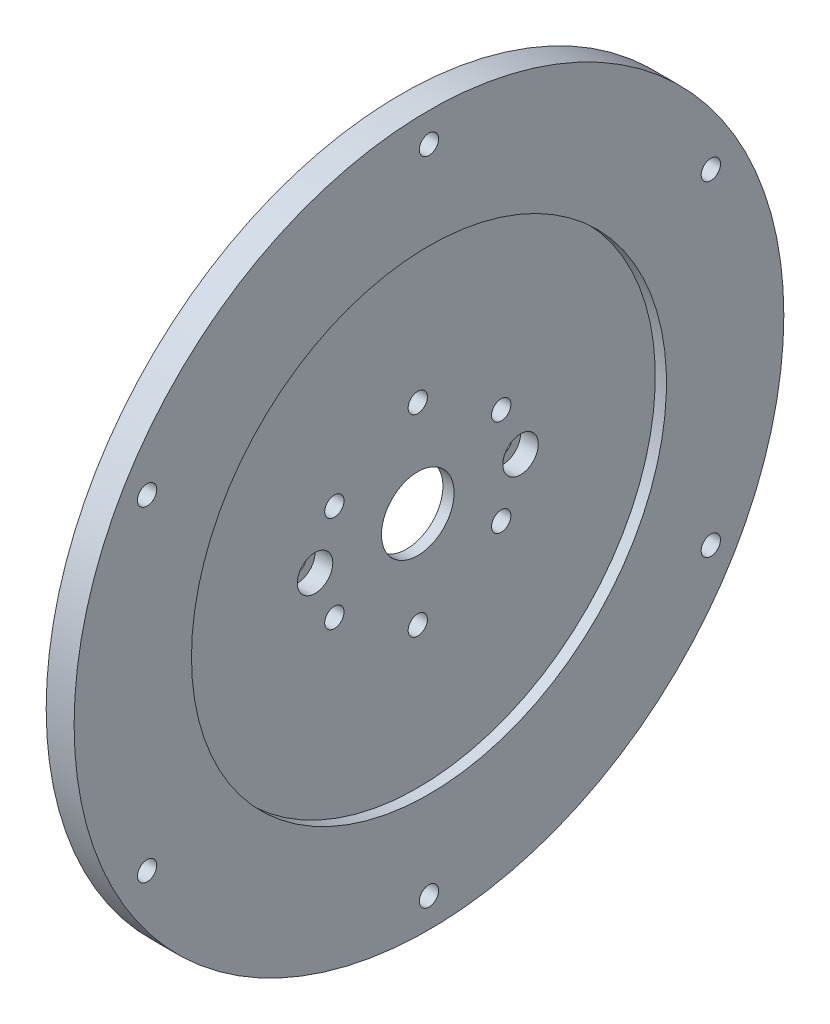
SolidWorks part; units mm, degrees
ref_plane "Front Plane" through (0, 0, 0) normal (0, 0, 1) x (1, 0, 0)
ref_plane "Top Plane" through (0, 0, 0) normal (0, 1, 0) x (1, 0, 0)
ref_plane "Right Plane" through (0, 0, 0) normal (1, 0, 0) x (0, 0, -1)
sketch "Sketch1" plane through (0, 0, 0) normal (0, 0, 1) x (1, 0, 0)
  line L0 (0, 0) -> (58.591, 0) construction
  line L2 (0, 0) -> (19, 0)
  line L3 (0, 0) -> (0, 2.5)
  line L4 (0, 2.5) -> (19, 2.5)
  line L5 (19, 0) -> (19, 2.5)
  line L6 (6, 2.5) -> (6, 6)
  line L11 (6, 6) -> (10, 6)
  line L16 (13, 6) -> (13, 3)
  line L17 (13, 3) -> (13.6604, 3)
  line L18 (13.6604, 3) -> (13.6604, 2.5)
  line L19 (13.6604, 2.5) -> (6, 2.5)
  line L22 (13.6604, 2.5) -> (16.1604, 2.5)
  line L23 (13.6604, 2.5) -> (13.6604, 4)
  line L24 (13.6604, 4) -> (16.1604, 4)
  line L25 (16.1604, 2.5) -> (16.1604, 4)
  line L27 (6, 6) -> (10, 6)
  line L28 (6, 6) -> (6, 9)
  line L29 (6, 9) -> (10, 9)
  line L30 (10, 6) -> (10, 9)
  line L31 (6, 9) -> (6, 8.25)
  line L32 (6, 8.25) -> (5, 8.25)
  line L33 (8.58, 22.001) -> (8.58, 12.476) construction
  line L34 (5, 12.476) -> (12.16, 12.476)
  line L35 (10, 9) -> (12.16, 9)
  line L36 (5, 7.5) -> (3, 7.5)
  line L37 (5, 8.25) -> (5, 12.476)
  line L38 (5, 7.5) -> (5, 14)
  line L39 (5, 14) -> (3, 14)
  line L40 (3, 7.5) -> (3, 14)
  line L41 (5, 22.001) -> (12.16, 22.001)
  line L42 (5, 22.001) -> (5, 30.1625)
  line L43 (5, 30.1625) -> (12.16, 30.1625)
  line L44 (12.16, 22.001) -> (12.16, 30.1625)
  line L49 (16.6604, 22.001) -> (16.6604, 7.5)
  line L51 (23.0604, 7.5) -> (23.0604, 6.5)
  line L54 (16.1604, 4) -> (13.6604, 4)
  line L56 (18.0604, 7.5) -> (23.0604, 7.5)
  line L57 (13.16, 22.001) -> (16.6604, 22.001)
  line L58 (16.1604, 3.5) -> (20.0604, 3.5)
  line L59 (29.9604, 14) -> (27.2104, 11.25)
  line L60 (4, 31.75) -> (18.0604, 31.75)
  line L61 (18.0604, 7.5) -> (23.0604, 7.5)
  line L62 (18.0604, 7.5) -> (18.0604, 12)
  line L63 (18.0604, 12) -> (23.0604, 12)
  line L64 (23.0604, 7.5) -> (23.0604, 12)
  line L65 (18.0604, 31.75) -> (18.0604, 12)
  line L66 (23.0604, 11.25) -> (27.2104, 11.25)
  line L67 (34.8604, 23) -> (31.8604, 20)
  line L68 (35.8604, 31) -> (38.8604, 34)
  line L69 (29.9604, 14) -> (29.9604, 15)
  line L70 (29.9604, 15) -> (22.9604, 15)
  line L71 (22.9604, 15) -> (21.0604, 15)
  line L72 (18.0604, 7.5) -> (16.6604, 7.5)
  line L73 (21.0604, 15) -> (21.0604, 42.5)
  line L74 (20.0604, 40) -> (10.0604, 40)
  line L75 (10.0604, 40) -> (4, 40)
  line L76 (21.0604, 42.5) -> (20.0604, 42.5)
  line L77 (22.9604, 15) -> (29.9604, 15)
  line L78 (22.9604, 15) -> (22.9604, 21)
  line L79 (22.9604, 21) -> (29.9604, 21)
  line L80 (29.9604, 15) -> (29.9604, 21)
  line L81 (10.0604, 40) -> (20.0604, 40)
  line L82 (10.0604, 40) -> (10.0604, 50)
  line L83 (10.0604, 50) -> (20.0604, 50)
  line L84 (20.0604, 40) -> (20.0604, 50)
  line L85 (4, 40) -> (4, 31.75)
  line L86 (13, 3) -> (13, 2.5)
  line L87 (31.8604, 20) -> (29.9604, 20)
  line L88 (21.51, 63.5) -> (21.51, 43.5)
  line L89 (21.51, 63.5) -> (25.9604, 63.5)
  line L90 (25.9604, 63.5) -> (25.9604, 25)
  line L91 (27.8604, 25) -> (25.9604, 25)
  line L92 (10.0604, 48) -> (9, 48)
  line L93 (9, 48) -> (9, 53.476)
  line L94 (9, 53.476) -> (20.0604, 53.476)
  line L95 (20.0604, 53.476) -> (20.0604, 50)
  line L96 (14.5302, 63.001) -> (14.5302, 53.476) construction
  line L97 (9, 63.001) -> (20.0604, 63.001)
  line L98 (9, 63.001) -> (9, 68.2625)
  line L99 (9, 68.2625) -> (20.0604, 68.2625)
  line L100 (20.0604, 63.001) -> (20.0604, 68.2625)
  line L101 (13, 6) -> (12, 6)
  line L102 (9, 42.5) -> (5, 42.5)
  line L103 (9, 42.5) -> (9, 55)
  line L104 (9, 55) -> (5, 55)
  line L105 (5, 42.5) -> (5, 55)
  line L106 (10, 6) -> (10.9, 6)
  line L107 (27.8604, 25) -> (34.8604, 25)
  line L108 (34.8604, 25) -> (34.8604, 23)
  line L109 (0, 0) -> (-2, 0)
  line L110 (0, 0) -> (0, 11)
  line L111 (27.8604, 25) -> (34.8604, 25)
  line L112 (27.8604, 25) -> (27.8604, 32.5)
  line L113 (27.8604, 32.5) -> (34.8604, 32.5)
  line L114 (34.8604, 25) -> (34.8604, 32.5)
  line L115 (35.8604, 31) -> (34.8604, 31)
  line L116 (27.8604, 32.5) -> (27.8604, 64.5)
  line L117 (21.0604, 74.025) -> (7, 74.025)
  line L118 (7, 74.025) -> (7, 76.2)
  line L119 (38.8604, 47.28) -> (30.8604, 55.28)
  line L120 (0, 11) -> (-2, 11)
  line L121 (38.8604, 43.815) -> (30.9229, 43.815)
  line L123 (-4.9, 76.2) -> (7, 76.2)
  line L124 (38.8604, 47.28) -> (38.8604, 34)
  line L125 (-2, 0) -> (-2, 11)
  line L126 (38.8604, 37.465) -> (30.9229, 37.465)
  line L127 (30.9229, 43.815) -> (30.9229, 37.465)
  line L128 (6, 2.5) -> (6, 0)
  line L129 (0, 63.5) -> (0, 30)
  line L132 (5, 63.5) -> (0, 63.5)
  line L136 (-1.9, 30) -> (-11.9, 30)
  line L137 (-11.9, 30) -> (-11.9, 25.4)
  line L138 (-11.9, 25.4) -> (-2, 25.4)
  line L139 (-2, 25.4) -> (-2, 11.5)
  line L140 (27.8604, 64.5) -> (21.0604, 64.5)
  line L141 (-1.9, 30) -> (-11.9, 30)
  line L142 (-1.9, 30) -> (-1.9, 39)
  line L143 (-1.9, 39) -> (-11.9, 39)
  line L144 (-11.9, 30) -> (-11.9, 39)
  line L145 (21.0604, 64.5) -> (21.0604, 74.025)
  line L146 (-12.9, 37) -> (-12.9, 47.28)
  line L147 (-12.9, 37) -> (-11.9, 37)
  line L148 (30.8604, 55.28) -> (30.8604, 76.2)
  line L149 (12, 6) -> (12, 5.45)
  line L154 (-2, 11.5) -> (1, 11.5)
  line L155 (5, 60.6197) -> (24.05, 60.6197)
  line L160 (5, 60.6197) -> (5, 55.8572)
  line L161 (5, 55.8572) -> (24.05, 55.8572)
  line L166 (24.05, 60.6197) -> (24.05, 55.8572)
  line L167 (5, 60.6197) -> (24.05, 55.8572) construction
  line L172 (5, 55.8572) -> (24.05, 60.6197) construction
  line L173 (24.05, 62.2072) -> (25.9604, 62.2072)
  line L174 (12, 5.45) -> (10.9, 5.45)
  line L175 (10.9, 6) -> (10.9, 5.45)
  line L176 (24.05, 62.2072) -> (24.05, 54.2697)
  line L177 (24.05, 54.2697) -> (25.9604, 54.2697)
  line L178 (25.9604, 62.2072) -> (25.9604, 54.2697)
  line L179 (24.05, 62.2072) -> (25.9604, 54.2697) construction
  line L180 (24.05, 54.2697) -> (25.9604, 62.2072) construction
  line L181 (3, 19.6197) -> (15.7, 19.6197)
  line L182 (3, 19.6197) -> (3, 14.8572)
  line L183 (3, 14.8572) -> (15.7, 14.8572)
  line L184 (15.7, 19.6197) -> (15.7, 14.8572)
  line L185 (3, 19.6197) -> (15.7, 14.8572) construction
  line L186 (3, 14.8572) -> (15.7, 19.6197) construction
  line L187 (15.7, 21.2072) -> (16.6604, 21.2072)
  line L188 (15.7, 21.2072) -> (15.7, 13.2697)
  line L189 (15.7, 13.2697) -> (16.6604, 13.2697)
  line L190 (16.6604, 21.2072) -> (16.6604, 13.2697)
  line L191 (15.7, 21.2072) -> (16.6604, 13.2697) construction
  line L192 (15.7, 13.2697) -> (16.6604, 21.2072) construction
  line L193 (1, 11.5) -> (1, 6.5)
  line L194 (1, 6.5) -> (3, 6.5)
  line L195 (23.0604, 6.5) -> (20.0604, 3.5)
  line L196 (5, 63.5) -> (5, 42.5)
  line L197 (5, 42.5) -> (3, 42.5)
  line L198 (3, 42.5) -> (3, 6.5)
  line L199 (6, 0) -> (13, 0)
  line L200 (13, 0) -> (13, 2.5)
  line L201 (18.0604, 31.75) -> (18.0604, 35.875)
  line L202 (18.0604, 35.875) -> (21.0604, 35.875)
  line L203 (30.8604, 76.2) -> (7, 76.2)
  line L204 (3.4177, 69.85) -> (8, 69.85) construction
  line L205 (8, 67.4687) -> (27.05, 67.4688)
  line L206 (8, 74.025) -> (8, 64.5)
  line L207 (8, 64.5) -> (-1.9, 64.5)
  line L208 (-1.9, 64.5) -> (-1.9, 39)
  line L209 (-12.9, 47.28) -> (-4.9, 55.28)
  line L210 (-4.9, 55.28) -> (-4.9, 76.2)
  line L211 (8, 67.4687) -> (8, 72.2313)
  line L212 (8, 72.2313) -> (27.05, 72.2313)
  line L213 (27.05, 67.4688) -> (27.05, 72.2313)
  line L214 (27.05, 73.8187) -> (30.8604, 73.8187)
  line L215 (27.05, 73.8187) -> (27.05, 65.8813)
  line L216 (27.05, 65.8813) -> (30.8604, 65.8813)
  line L217 (30.8604, 73.8187) -> (30.8604, 65.8813)
  line L218 (3.4177, 72.2313) -> (25.6427, 72.2313)
  line L219 (3.4177, 72.2313) -> (3.4177, 67.4688)
  line L220 (3.4177, 67.4688) -> (25.6427, 67.4688)
  line L221 (25.6427, 72.2313) -> (25.6427, 67.4688)
  line L222 (25.6427, 69.85) -> (21.0604, 69.85) construction
  line L223 (21.51, 43.5) -> (22.9604, 43.5)
  line L224 (22.9604, 43.5) -> (22.9604, 21)
  line L225 (13.6604, 4) -> (13.6604, 12.2697)
  line L226 (13.6604, 12.2697) -> (13.16, 12.2697)
  line L227 (13.16, 12.2697) -> (13.16, 22.001)
  line L228 (12.16, 9) -> (12.16, 12.476)
  line L229 (-1.9, 30) -> (0, 30)
  circle A0 centre (26.9104, 25.95) radius 0.95
  circle A1 centre (22.0104, 15.95) radius 0.95
  circle A2 centre (17.3604, 8.2) radius 0.7
  circle A3 centre (10.45, 6.45) radius 0.45
  circle A4 centre (-0.95, 30.95) radius 0.95
  point P7 (25.0052, 58.2385)
  point P131 (16.1802, 17.2385)
  point P135 (14.525, 58.2385)
  point P146 (9.35, 17.2385)
sketch "Sketch2" plane through (0, 0, 0) normal (0, 0, 1) x (1, 0, 0)
  line L0 (-1.9, 30) -> (-11.9, 30) construction
  line L1 (-2, 25.4) -> (-2, 11.5) construction
  line L2 (-11.9, 30) -> (-11.9, 25.4) construction
  line L3 (-11.9, 25.4) -> (-2, 25.4) construction
  line L4 (-2, 11.5) -> (1, 11.5) construction
  line L5 (1, 11.5) -> (1, 6.5) construction
  line L6 (1, 6.5) -> (3, 6.5) construction
  line L7 (3, 42.5) -> (3, 6.5) construction
  line L8 (5, 42.5) -> (3, 42.5) construction
  line L9 (5, 63.5) -> (5, 42.5) construction
  line L10 (5, 63.5) -> (0, 63.5) construction
  line L11 (0, 63.5) -> (0, 30) construction
  line L14 (-1.9, 30) -> (-11.9, 30)
  line L15 (-2, 25.4) -> (-2, 11.5)
  line L16 (-11.9, 30) -> (-11.9, 25.4)
  line L17 (-11.9, 25.4) -> (-2, 25.4)
  line L18 (-2, 11.5) -> (1, 11.5)
  line L19 (1, 11.5) -> (1, 6.5)
  line L20 (1, 6.5) -> (3, 6.5)
  line L21 (3, 42.5) -> (3, 6.5)
  line L22 (5, 42.5) -> (3, 42.5)
  line L23 (5, 63.5) -> (5, 42.5)
  line L24 (5, 63.5) -> (0, 63.5)
  line L25 (0, 63.5) -> (0, 30)
  line L28 (-1.9, 30) -> (0, 30) construction
  line L29 (-1.9, 30) -> (0, 30)
revolve "Revolve1" add sketch "Sketch2" angle 360 about L0 region at (0.2358, 35.0905, 0)
sketch "Sketch3" plane through (0, 0, 0) normal (1, 0, 0) x (0, 0, -1)
  line L0 (0, 0) -> (0, 69.85) construction
  line L1 (0, 0) -> (13.6271, 68.5079) construction
  line L2 (0, 0) -> (0, 58.2385) construction
  line L3 (0, 0) -> (50.436, 29.1192) construction
  line L4 (0, 0) -> (0, 31.75) construction
  line L5 (0, 0) -> (12.1502, 29.3332) construction
  line L6 (0, 0) -> (0, 17.2385) construction
  line L7 (0, 0) -> (14.929, 8.6192) construction
  line L8 (0, 0) -> (0, 58.2385) construction
  line L9 (0, 0) -> (50.436, 29.1192) construction
  line L10 (0, 0) -> (5.9583, 29.9542) construction
  line L11 (0, 0) -> (16.9677, 25.394) construction
  circle A0 centre (0, 0) radius 69.85 construction
  circle A1 centre (0, 0) radius 58.2385 construction
  circle A2 centre (0, 0) radius 31.75 construction
  circle A3 centre (0, 0) radius 17.2385 construction
  circle A4 centre (0, 69.85) radius 3.175
  circle A5 centre (0, 58.2385) radius 4.7625
  circle A6 centre (0, 31.75) radius 3.175
  circle A7 centre (0, 17.2385) radius 4.7625
  circle A8 centre (13.6271, 68.5079) radius 3.175
  circle A9 centre (26.7304, 64.533) radius 3.175
  circle A10 centre (38.8066, 58.0782) radius 3.175
  circle A11 centre (49.3914, 49.3914) radius 3.175
  circle A12 centre (58.0782, 38.8066) radius 3.175
  circle A13 centre (64.533, 26.7304) radius 3.175
  circle A14 centre (68.5079, 13.6271) radius 3.175
  circle A15 centre (69.85, 0) radius 3.175
  circle A16 centre (68.5079, -13.6271) radius 3.175
  circle A17 centre (64.533, -26.7304) radius 3.175
  circle A18 centre (58.0782, -38.8066) radius 3.175
  circle A19 centre (49.3914, -49.3914) radius 3.175
  circle A20 centre (38.8066, -58.0782) radius 3.175
  circle A21 centre (26.7304, -64.533) radius 3.175
  circle A22 centre (13.6271, -68.5079) radius 3.175
  circle A23 centre (0, -69.85) radius 3.175
  circle A24 centre (-13.6271, -68.5079) radius 3.175
  circle A25 centre (-26.7304, -64.533) radius 3.175
  circle A26 centre (-38.8066, -58.0782) radius 3.175
  circle A27 centre (-49.3914, -49.3914) radius 3.175
  circle A28 centre (-58.0782, -38.8066) radius 3.175
  circle A29 centre (-64.533, -26.7304) radius 3.175
  circle A30 centre (-68.5079, -13.6271) radius 3.175
  circle A31 centre (-69.85, 0) radius 3.175
  circle A32 centre (-68.5079, 13.6271) radius 3.175
  circle A33 centre (-64.533, 26.7304) radius 3.175
  circle A34 centre (-58.0782, 38.8066) radius 3.175
  circle A35 centre (-49.3914, 49.3914) radius 3.175
  circle A36 centre (-38.8066, 58.0782) radius 3.175
  circle A37 centre (-26.7304, 64.533) radius 3.175
  circle A38 centre (-13.6271, 68.5079) radius 3.175
  circle A47 centre (50.436, 29.1192) radius 4.7625
  circle A48 centre (50.436, -29.1192) radius 4.7625
  circle A49 centre (0, -58.2385) radius 4.7625
  circle A50 centre (-50.436, -29.1192) radius 4.7625
  circle A51 centre (-50.436, 29.1192) radius 4.7625
  circle A58 centre (12.1502, 29.3332) radius 3.175
  circle A59 centre (22.4506, 22.4506) radius 3.175
  circle A60 centre (29.3332, 12.1502) radius 3.175
  circle A61 centre (31.75, 0) radius 3.175
  circle A62 centre (29.3332, -12.1502) radius 3.175
  circle A63 centre (22.4506, -22.4506) radius 3.175
  circle A64 centre (12.1502, -29.3332) radius 3.175
  circle A65 centre (0, -31.75) radius 3.175
  circle A66 centre (-12.1502, -29.3332) radius 3.175
  circle A67 centre (-22.4506, -22.4506) radius 3.175
  circle A68 centre (-29.3332, -12.1502) radius 3.175
  circle A69 centre (-31.75, 0) radius 3.175
  circle A70 centre (-29.3332, 12.1502) radius 3.175
  circle A71 centre (-22.4506, 22.4506) radius 3.175
  circle A72 centre (14.929, 8.6192) radius 4.7625
  circle A73 centre (14.929, -8.6192) radius 4.7625
  circle A74 centre (0, -17.2385) radius 4.7625
  circle A75 centre (-14.929, -8.6192) radius 4.7625
  circle A76 centre (-14.929, 8.6192) radius 4.7625
  circle A77 centre (0, 0) radius 50
  circle A78 centre (0, 0) radius 9
  circle A79 centre (-12.1502, 29.3332) radius 3.175
  circle A80 centre (0, 0) radius 76.2
  circle A81 centre (0, 0) radius 74.025
  circle A82 centre (0, 69.85) radius 3.9687
  circle A83 centre (49.3914, 49.3914) radius 3.9687
  circle A84 centre (69.85, 0) radius 3.9688
  circle A85 centre (49.3914, -49.3914) radius 3.9687
  circle A86 centre (0, -69.85) radius 3.9687
  circle A87 centre (-49.3914, -49.3914) radius 3.9687
  circle A88 centre (-69.85, 0) radius 3.9688
  circle A89 centre (-49.3914, 49.3914) radius 3.9687
  circle A90 centre (0, 69.85) radius 2.3812
  circle A91 centre (13.6271, 68.5079) radius 2.3812
  circle A92 centre (26.7304, 64.533) radius 2.3813
  circle A93 centre (38.8066, 58.0782) radius 2.3812
  circle A94 centre (49.3914, 49.3914) radius 2.3812
  circle A95 centre (58.0782, 38.8066) radius 2.3812
  circle A96 centre (64.533, 26.7304) radius 2.3813
  circle A97 centre (68.5079, 13.6271) radius 2.3813
  circle A98 centre (69.85, 0) radius 2.3813
  circle A99 centre (68.5079, -13.6271) radius 2.3813
  circle A100 centre (64.533, -26.7304) radius 2.3813
  circle A101 centre (58.0782, -38.8066) radius 2.3812
  circle A102 centre (49.3914, -49.3914) radius 2.3812
  circle A103 centre (38.8066, -58.0782) radius 2.3812
  circle A104 centre (26.7304, -64.533) radius 2.3813
  circle A105 centre (13.6271, -68.5079) radius 2.3812
  circle A106 centre (0, -69.85) radius 2.3812
  circle A107 centre (-13.6271, -68.5079) radius 2.3812
  circle A108 centre (-26.7304, -64.533) radius 2.3813
  circle A109 centre (-38.8066, -58.0782) radius 2.3812
  circle A110 centre (-49.3914, -49.3914) radius 2.3812
  circle A111 centre (-58.0782, -38.8066) radius 2.3812
  circle A112 centre (-64.533, -26.7304) radius 2.3812
  arc A113 (3.0399, 30.8338) -> (8.9911, 29.65) centre (5.9583, 29.9542) cw
  arc A114 (14.6081, 27.3234) -> (19.6532, 23.9523) centre (16.9677, 25.394) cw
  arc A115 (23.9523, 19.6532) -> (27.3234, 14.6081) centre (25.394, 16.9677) cw
  arc A116 (29.65, 8.9911) -> (30.8338, 3.0399) centre (29.9542, 5.9583) cw
  arc A117 (30.8338, -3.0399) -> (29.65, -8.9911) centre (29.9542, -5.9583) cw
  arc A118 (27.3234, -14.6081) -> (23.9523, -19.6532) centre (25.394, -16.9677) cw
  arc A119 (19.6532, -23.9523) -> (14.6081, -27.3234) centre (16.9677, -25.394) cw
  arc A120 (8.9911, -29.65) -> (3.0399, -30.8338) centre (5.9583, -29.9542) cw
  arc A121 (-3.0399, -30.8338) -> (-8.9911, -29.65) centre (-5.9583, -29.9542) cw
  arc A122 (-14.6081, -27.3234) -> (-19.6532, -23.9523) centre (-16.9677, -25.394) cw
  arc A123 (-23.9523, -19.6532) -> (-27.3234, -14.6081) centre (-25.394, -16.9677) cw
  arc A124 (-29.65, -8.9911) -> (-30.8338, -3.0399) centre (-29.9542, -5.9583) cw
  arc A125 (-30.8338, 3.0399) -> (-29.65, 8.9911) centre (-29.9542, 5.9583) cw
  arc A126 (-27.3234, 14.6081) -> (-23.9523, 19.6532) centre (-25.394, 16.9677) cw
  arc A127 (-19.6532, 23.9523) -> (-14.6081, 27.3234) centre (-16.9677, 25.394) cw
  arc A128 (-8.9911, 29.65) -> (-3.0399, 30.8338) centre (-5.9583, 29.9542) cw
  arc A129 (26.9875, 0) -> (26.9932, 0.1932) centre (30.2705, 0) cw
  arc A130 (65.0988, 0.2771) -> (65.0875, 0) centre (68.4964, 0) ccw
  circle A131 centre (1.5875, 0) radius 40
  circle A132 centre (1.5875, 0) radius 2.5
  circle A133 centre (1.5875, 0) radius 3
  circle A134 centre (1.5875, 0) radius 41
  circle A135 centre (-68.5079, -13.6271) radius 2.3813
  circle A136 centre (-69.85, 0) radius 2.3813
  circle A137 centre (-68.5079, 13.6271) radius 2.3813
  circle A138 centre (-64.533, 26.7304) radius 2.3812
  circle A139 centre (-58.0782, 38.8066) radius 2.3812
  circle A140 centre (-49.3914, 49.3914) radius 2.3812
  circle A141 centre (-38.8066, 58.0782) radius 2.3812
  circle A142 centre (-26.7304, 64.533) radius 2.3813
  circle A143 centre (-13.6271, 68.5079) radius 2.3812
  circle A144 centre (0, 58.2385) radius 2.3812
  circle A145 centre (0, 58.2385) radius 3.9688
  circle A146 centre (50.436, 29.1192) radius 3.9688
  circle A147 centre (50.436, 29.1192) radius 2.3813
  circle A148 centre (50.436, -29.1192) radius 3.9687
  circle A149 centre (50.436, -29.1192) radius 2.3812
  circle A150 centre (0, -58.2385) radius 3.9687
  circle A151 centre (0, -58.2385) radius 2.3812
  circle A152 centre (-50.436, -29.1192) radius 3.9687
  circle A153 centre (-50.436, -29.1192) radius 2.3812
  circle A154 centre (-50.436, 29.1192) radius 3.9687
  circle A155 centre (-50.436, 29.1192) radius 2.3812
  spline S1 degree 4 poles (26.9875, 0) (26.9875, -0.0248) (26.9882, -0.0743) (26.9912, -0.1613) (26.9992, -0.2849) (27.0142, -0.4323) (27.0403, -0.5994) (27.0821, -0.7965) (27.1455, -1.0177) (27.2241, -1.2336) (27.3173, -1.4437) (27.4329, -1.6623) (27.5739, -1.8864) (27.7427, -2.1125) (27.9417, -2.3365) (28.1305, -2.5184) (28.3007, -2.6647) (28.4457, -2.7828) (28.5617, -2.8775) (28.6745, -2.9758) (28.7813, -3.0807) (28.9057, -3.2206) (29.0482, -3.4108) (29.197, -3.6576) (29.3758, -4.0447) (29.5291, -4.5502) (29.6152, -5.1612) (29.5933, -5.8758) (29.4507, -6.5869) (29.186, -7.2733) (28.8461, -7.831) (28.4818, -8.2549) (28.1375, -8.5536) (27.8792, -8.7284) (27.6484, -8.8496) (27.4154, -8.9438) (27.2144, -9.0029) (27.0118, -9.0554) (26.7709, -9.1263) (26.5334, -9.2082) (26.2634, -9.3231) (25.9685, -9.4827) (25.5538, -9.7623) (25.0678, -10.2216) (24.6281, -10.8948) (24.3613, -11.7878) (24.3459, -12.6097) (24.4764, -13.2366) (24.6525, -13.7006) (24.8058, -14.0202) (24.9382, -14.271) (25.0503, -14.5321) (25.1258, -14.8064) (25.1736, -15.0995) (25.1911, -15.4094) (25.1742, -15.8163) (25.0891, -16.3148) (24.907, -16.8764) (24.5182, -17.6315) (23.9757, -18.2942) (23.3695, -18.7764) (22.7564, -19.084) (22.3641, -19.2199) (22.0554, -19.2923) (21.7533, -19.3289) (21.4612, -19.3296) (21.1723, -19.2896) (20.8852, -19.2417) (20.5956, -19.2104) (20.3043, -19.1994) (19.8669, -19.2177) (19.2899, -19.3231) (18.5833, -19.6092) (17.8444, -20.1834) (17.3807, -20.828) (17.1316, -21.424) (17.0182, -21.8879) (16.9714, -22.1971) (16.9537, -22.4701) (16.9533, -22.7044) (16.9619, -22.9384) (16.9737, -23.1333) (16.977, -23.3286) (16.9594, -23.5624) (16.9177, -23.8101) (16.834, -24.1055) (16.6578, -24.5276) (16.3623, -25.0151) (15.9278, -25.5198) (15.3432, -25.99) (14.6957, -26.3472) (14.0068, -26.5857) (13.3856, -26.6851) (12.847, -26.6849) (12.4166, -26.6224) (12.1324, -26.5468) (11.9058, -26.4598) (11.7342, -26.3753) (11.6017, -26.2989) (11.4727, -26.2169) (11.3444, -26.1337) (11.1825, -26.0322) (10.9836, -25.9179) (10.7435, -25.7991) (10.4587, -25.6867) (10.0106, -25.5536) (9.3843, -25.468) (8.599, -25.5363) (7.7243, -25.8773) (7.1093, -26.3459) (6.716, -26.8042) (6.4745, -27.1841) (6.3352, -27.4489) (6.215, -27.7227) (6.1113, -28.0028) (5.9959, -28.2789) (5.841, -28.5357) (5.6522, -28.7792) (5.4316, -29.007) (5.1188, -29.2711) (4.6965, -29.5439) (4.1624, -29.7882) (3.5487, -29.9564) (2.9521, -30.0296) (2.386, -30.0225) (1.8595, -29.949) (1.3409, -29.8055) (0.9058, -29.6147) (0.5544, -29.4004) (0.2828, -29.1832) (0.0847, -28.9875) (-0.0865, -28.768) (-0.2353, -28.5332) (-0.3904, -28.3016) (-0.5598, -28.0786) (-0.792, -27.8146) (-1.1036, -27.5274) (-1.5105, -27.2448) (-2.0688, -26.9834) (-2.7167, -26.8202) (-3.459, -26.7949) (-4.1529, -26.9407) (-4.7224, -27.1899) (-5.1296, -27.455) (-5.3866, -27.661) (-5.5925, -27.8507) (-5.7558, -28.014) (-5.9199, -28.1766) (-6.0977, -28.3246) (-6.3382, -28.4851) (-6.6906, -28.6628) (-7.1669, -28.8182) (-7.7668, -28.9076) (-8.4201, -28.8957) (-9.0747, -28.7804) (-9.7144, -28.5614) (-10.3217, -28.2381) (-10.8061, -27.8636) (-11.1671, -27.4837) (-11.4143, -27.1402) (-11.5734, -26.859) (-11.6946, -26.573) (-11.7735, -26.2857) (-11.8173, -25.9915) (-11.8668, -25.6988) (-11.9353, -25.4093) (-12.0257, -25.1261) (-12.198, -24.7091) (-12.5089, -24.187) (-13.0379, -23.6191) (-13.8448, -23.1355) (-14.6072, -22.9365) (-15.2369, -22.9149) (-15.701, -22.9694) (-16.0024, -23.0316) (-16.2609, -23.107) (-16.4782, -23.1841) (-16.6576, -23.2529) (-16.8015, -23.307) (-16.9839, -23.3672) (-17.2087, -23.4203) (-17.4853, -23.4534) (-17.811, -23.4543) (-18.2291, -23.4104) (-18.7305, -23.2885) (-19.2884, -23.06) (-19.8603, -22.7052) (-20.3581, -22.2764) (-20.7758, -21.7899) (-21.1086, -21.2598) (-21.3336, -20.7318) (-21.4619, -20.2263) (-21.5006, -19.8113) (-21.4889, -19.4989) (-21.4468, -19.2424) (-21.3965, -19.0408) (-21.34, -18.8332) (-21.2878, -18.6168) (-21.2341, -18.3322) (-21.1962, -17.9773) (-21.1985, -17.5604) (-21.2781, -17.0173) (-21.4721, -16.4256) (-21.838, -15.7861) (-22.3482, -15.2578) (-22.8946, -14.8957) (-23.3828, -14.6878) (-23.7368, -14.5834) (-24.0536, -14.5215) (-24.3285, -14.4876) (-24.6045, -14.47) (-24.8811, -14.458) (-25.1556, -14.4184) (-25.4228, -14.3439) (-25.6932, -14.2375) (-26.1109, -14.0218) (-26.5677, -13.6822) (-27.0258, -13.1981) (-27.4314, -12.5682) (-27.7017, -11.9578) (-27.8746, -11.3112) (-27.9332, -10.727) (-27.9111, -10.2247) (-27.8415, -9.8214) (-27.7568, -9.5159) (-27.6427, -9.2298) (-27.5004, -8.9659) (-27.3212, -8.7261) (-27.1301, -8.4966) (-26.9071, -8.1967) (-26.6417, -7.7583) (-26.3997, -7.1508) (-26.2841, -6.3875) (-26.3642, -5.5798) (-26.6019, -4.9055) (-26.9193, -4.3761) (-27.2736, -3.9636) (-27.583, -3.6904) (-27.8719, -3.4871) (-28.1186, -3.3407) (-28.3135, -3.2371) (-28.5043, -3.1411) (-28.6854, -3.0419) (-28.9002, -2.8984) (-29.1355, -2.6958) (-29.4123, -2.3882) (-29.6958, -1.9552) (-29.932, -1.437) (-30.0985, -0.839) (-30.1779, -0.2025) (-30.1603, 0.4599) (-30.0348, 1.1323) (-29.8199, 1.711) (-29.5617, 2.1719) (-29.3035, 2.5118) (-29.0784, 2.748) (-28.8655, 2.924) (-28.6761, 3.0468) (-28.5112, 3.1367) (-28.3775, 3.205) (-28.2106, 3.2911) (-28.0136, 3.4005) (-27.7912, 3.5413) (-27.5508, 3.7219) (-27.2011, 4.0343) (-26.7941, 4.5285) (-26.4419, 5.234) (-26.2777, 6.1494) (-26.351, 6.9081) (-26.5268, 7.4739) (-26.7218, 7.8823) (-26.8619, 8.1196) (-26.9953, 8.3144) (-27.1373, 8.5028) (-27.2613, 8.6553) (-27.3845, 8.8088) (-27.518, 9.0035) (-27.6324, 9.2103) (-27.7412, 9.4693) (-27.8326, 9.7814) (-27.9074, 10.1885) (-27.9345, 10.6913) (-27.8808, 11.2771) (-27.6878, 12.0229) (-27.3166, 12.8111) (-26.8405, 13.4278) (-26.3243, 13.8718) (-25.9118, 14.1263) (-25.6503, 14.2566) (-25.3769, 14.3596) (-25.0933, 14.4318) (-24.8027, 14.4634) (-24.5112, 14.4738) (-24.1629, 14.5033) (-23.7608, 14.5717) (-23.1887, 14.7443) (-22.5511, 15.0901) (-21.962, 15.6231) (-21.544, 16.2749) (-21.3217, 16.857) (-21.2175, 17.3851) (-21.1902, 17.8397) (-21.2185, 18.2374) (-21.2771, 18.5739) (-21.3443, 18.8506) (-21.405, 19.0706) (-21.4579, 19.2928) (-21.4883, 19.5194) (-21.4981, 19.805) (-21.4664, 20.1907) (-21.3565, 20.6672) (-21.1331, 21.2135) (-20.8025, 21.7541) (-20.3882, 22.2461) (-19.8974, 22.677) (-19.3379, 23.033) (-18.7964, 23.2649) (-18.309, 23.3941) (-17.8981, 23.4483) (-17.5726, 23.4572) (-17.2924, 23.4331) (-17.0602, 23.3874) (-16.8337, 23.3199) (-16.6495, 23.2499) (-16.4659, 23.1791) (-16.2424, 23.1025) (-16.0156, 23.0362) (-15.7461, 22.9768) (-15.2967, 22.9185) (-14.7035, 22.9278) (-13.9592, 23.0948) (-13.1407, 23.5365) (-12.5805, 24.0908) (-12.2382, 24.6309) (-12.0505, 25.0599) (-11.9538, 25.3442) (-11.8892, 25.5989) (-11.8463, 25.8198) (-11.8162, 26.0048) (-11.7926, 26.153) (-11.7577, 26.3372) (-11.6989, 26.5548) (-11.5969, 26.8111) (-11.4414, 27.0975) (-11.1977, 27.4473) (-10.8392, 27.8343) (-10.3554, 28.2166) (-9.7549, 28.5431) (-9.1303, 28.7642) (-8.5, 28.8851) (-7.879, 28.911) (-7.3126, 28.8458) (-6.8128, 28.7091) (-6.4345, 28.54) (-6.1692, 28.378) (-5.9665, 28.2173) (-5.8163, 28.0752) (-5.6659, 27.9232) (-5.5067, 27.7699) (-5.2907, 27.5806) (-5.0072, 27.369) (-4.6509, 27.1597) (-4.148, 26.9513) (-3.5452, 26.8146) (-2.8302, 26.7991) (-2.0381, 26.9749) (-1.3495, 27.3225) (-0.8483, 27.741) (-0.5146, 28.1291) (-0.2991, 28.4338) (-0.1401, 28.6862) (0.0331, 28.93) (0.2405, 29.146) (0.4774, 29.3422) (0.7418, 29.5165) (1.1036, 29.7066) (1.5741, 29.882) (2.1471, 30.006) (2.8151, 30.041) (3.4791, 29.9721) (4.2039, 29.7804) (4.8064, 29.4933) (5.2708, 29.1628) (5.6049, 28.8311) (5.7894, 28.6062) (5.9424, 28.3744) (6.0642, 28.1249) (6.161, 27.8653) (6.2635, 27.608) (6.3813, 27.357) (6.5388, 27.0748) (6.7484, 26.7704) (7.0986, 26.3707) (7.6135, 25.9641) (8.2747, 25.644) (8.9962, 25.4959) (9.6181, 25.496) (10.1582, 25.5894) (10.5546, 25.7168) (10.8796, 25.8629) (11.1331, 26.0022) (11.3224, 26.1188) (11.5021, 26.2366) (11.6784, 26.3463) (11.9094, 26.4649) (12.2028, 26.5718) (12.6092, 26.6624) (13.1291, 26.6958) (13.7, 26.6444) (14.3062, 26.4914) (14.8974, 26.2443) (15.459, 25.9029) (15.9732, 25.4681) (16.3631, 25.0071) (16.6337, 24.567) (16.8044, 24.1822) (16.9036, 23.8716) (16.9571, 23.5978) (16.9755, 23.3672) (16.9741, 23.1748) (16.9669, 23.0211) (16.9571, 22.8289) (16.9512, 22.5982) (16.9599, 22.3287) (16.9946, 22.0224) (17.0874, 21.5638) (17.3043, 20.9714) (17.7315, 20.3087) (18.4426, 19.693) (19.1468, 19.3677) (19.739, 19.2351) (20.1882, 19.2012) (20.4852, 19.2034) (20.7812, 19.2282) (21.0745, 19.2719) (21.3675, 19.3208) (21.6648, 19.3336) (21.9737, 19.306) (22.2899, 19.241) (22.6922, 19.1116) (23.1641, 18.8854) (23.669, 18.5404) (24.1634, 18.0628) (24.569, 17.5219) (24.8807, 16.9345) (25.0937, 16.316) (25.184, 15.7743) (25.1924, 15.3317) (25.1581, 14.9969) (25.1154, 14.7695) (25.0522, 14.5468) (24.9658, 14.3321) (24.8616, 14.1257) (24.7568, 13.9198) (24.6402, 13.6649) (24.524, 13.3562) (24.3985, 12.886) (24.3389, 12.2663) (24.4166, 11.5605) (24.6979, 10.7931) (25.0952, 10.2042) (25.5426, 9.7706) (25.9551, 9.4883) (26.2689, 9.3208) (26.5627, 9.1971) (26.83, 9.1062) (27.1019, 9.0315) (27.3749, 8.9598) (27.6385, 8.8574) (27.887, 8.7225) (28.1969, 8.5098) (28.5449, 8.1936) (28.9002, 7.7549) (29.2229, 7.1817) (29.4529, 6.562) (29.5858, 5.9108) (29.6165, 5.2432) (29.5485, 4.659) (29.4188, 4.1725) (29.2636, 3.7931) (29.1144, 3.5129) (28.9404, 3.2582) (28.7432, 3.0317) (28.5155, 2.8371) (28.281, 2.6515) (28.0578, 2.4519) (27.8492, 2.2371) (27.6347, 1.9761) (27.4574, 1.7102) (27.3152, 1.4444) (27.2047, 1.1845) (27.1307, 0.9703) (27.0789, 0.7793) (27.0441, 0.6164) (27.021, 0.472) (27.0061, 0.351) (26.9981, 0.2662) (26.9946, 0.2176) (26.9932, 0.1932) knots 0.06864 0.06864 0.06864 0.06864 0.06864 0.069106 0.069571 0.070037 0.070502 0.071433 0.072364 0.073295 0.074226 0.075157 0.076088 0.077301 0.078514 0.079727 0.08094 0.081547 0.082153 0.08276 0.083366 0.083973 0.084579 0.085792 0.087214 0.088636 0.091479 0.094323 0.097166 0.100174 0.103182 0.10619 0.107694 0.109198 0.110555 0.111234 0.111912 0.113269 0.113948 0.114626 0.115983 0.11734 0.118697 0.120055 0.12408 0.128106 0.131537 0.134967 0.137266 0.138415 0.139565 0.140714 0.141863 0.143013 0.144162 0.145524 0.146885 0.149608 0.152331 0.155054 0.160594 0.163364 0.164749 0.166134 0.167314 0.168495 0.169675 0.170855 0.172035 0.173215 0.174395 0.175575 0.179125 0.182676 0.186612 0.190548 0.191813 0.193079 0.194345 0.195611 0.196244 0.196877 0.198142 0.198775 0.199408 0.200674 0.202207 0.203741 0.206808 0.209874 0.212941 0.21584 0.218738 0.221637 0.223086 0.224535 0.225775 0.226394 0.227014 0.227634 0.228253 0.228873 0.229493 0.230732 0.231971 0.233211 0.23445 0.238303 0.242155 0.245814 0.249472 0.250683 0.251894 0.253105 0.254316 0.255527 0.256738 0.257949 0.25916 0.260514 0.261868 0.264577 0.267285 0.269993 0.272142 0.27429 0.276439 0.278588 0.280839 0.281965 0.283091 0.284217 0.285343 0.286469 0.287595 0.288737 0.289879 0.292163 0.294447 0.296732 0.299827 0.302922 0.306383 0.308113 0.309844 0.31078 0.311716 0.312652 0.313588 0.314524 0.31546 0.317332 0.319969 0.322606 0.325244 0.327881 0.330703 0.333524 0.336346 0.337757 0.339168 0.340372 0.341576 0.34278 0.343984 0.345188 0.346392 0.347596 0.3488 0.352495 0.356189 0.36002 0.36385 0.365096 0.366342 0.367588 0.368834 0.369457 0.370079 0.370702 0.371325 0.372571 0.373817 0.375207 0.376596 0.379375 0.382154 0.384933 0.387459 0.389986 0.392513 0.39504 0.396723 0.398407 0.399249 0.400091 0.400932 0.401774 0.402737 0.4037 0.405625 0.407551 0.409476 0.412569 0.415662 0.41939 0.421254 0.423119 0.42424 0.425361 0.426483 0.427604 0.428726 0.429847 0.430969 0.43209 0.433431 0.437455 0.440138 0.44282 0.445528 0.448236 0.450943 0.452297 0.453651 0.454862 0.456073 0.457284 0.458495 0.459706 0.460916 0.463338 0.466783 0.470228 0.473297 0.476366 0.478273 0.480179 0.482085 0.483038 0.483991 0.484828 0.485664 0.486501 0.487337 0.48901 0.490683 0.493189 0.495695 0.498202 0.500708 0.503552 0.506397 0.509241 0.510663 0.512085 0.513303 0.514521 0.51513 0.515738 0.516347 0.516956 0.518174 0.519391 0.520609 0.521827 0.525766 0.529706 0.533208 0.53671 0.537985 0.53926 0.540535 0.541173 0.54181 0.543085 0.543723 0.54436 0.545635 0.54691 0.548267 0.549623 0.552335 0.555047 0.55776 0.562061 0.566363 0.567545 0.568728 0.56991 0.571092 0.572275 0.573457 0.574639 0.575822 0.577939 0.580057 0.584292 0.587472 0.590653 0.592493 0.594334 0.596174 0.598014 0.59894 0.599865 0.60079 0.601715 0.60264 0.603565 0.605415 0.607973 0.610531 0.61309 0.615648 0.618364 0.62108 0.623796 0.625154 0.626512 0.627788 0.629065 0.629703 0.630341 0.631618 0.632256 0.632895 0.634171 0.635448 0.636724 0.640232 0.643739 0.647674 0.651609 0.652825 0.65404 0.655256 0.656472 0.65708 0.657688 0.658296 0.658904 0.66012 0.661336 0.662756 0.664177 0.667018 0.669858 0.672699 0.675209 0.677718 0.680227 0.682736 0.684412 0.686087 0.686924 0.687762 0.688599 0.689437 0.690391 0.691345 0.693254 0.695162 0.697071 0.700143 0.703216 0.706655 0.710095 0.712514 0.713723 0.714933 0.716142 0.717352 0.718561 0.719771 0.721123 0.722475 0.725179 0.727883 0.730587 0.733273 0.735959 0.739989 0.741332 0.742455 0.743577 0.7447 0.745823 0.746945 0.748068 0.749191 0.750314 0.752181 0.754048 0.757782 0.760871 0.763961 0.765883 0.767806 0.769729 0.77069 0.771651 0.772492 0.773333 0.774174 0.775015 0.776698 0.77838 0.780903 0.783427 0.785951 0.788475 0.791257 0.794039 0.796822 0.798213 0.799604 0.800852 0.802099 0.802723 0.803347 0.803971 0.804595 0.805842 0.80709 0.808337 0.809585 0.81342 0.817255 0.820945 0.824634 0.825837 0.827039 0.828242 0.829444 0.830647 0.831849 0.833052 0.834254 0.835663 0.837072 0.83989 0.842708 0.845526 0.848167 0.850807 0.853447 0.856087 0.857024 0.857961 0.858897 0.859834 0.860771 0.861707 0.862644 0.863581 0.865314 0.867048 0.870515 0.873613 0.876711 0.880181 0.881916 0.883651 0.884794 0.885937 0.887081 0.888224 0.889367 0.89051 0.891653 0.892797 0.895451 0.898105 0.90076 0.903414 0.906126 0.908838 0.911549 0.912905 0.914261 0.915474 0.916686 0.917899 0.919111 0.920323 0.921536 0.922748 0.923961 0.925793 0.926709 0.927625 0.928541 0.929457 0.929915 0.930373 0.930831 0.931289 0.931289 0.931289 0.931289 0.931289
  spline S3 degree 4 poles (65.0875, 0) (65.0875, -0.2085) (65.1336, -0.6093) (65.3196, -1.4523) (65.739, -2.0447) (66.242, -2.6341) (66.7299, -3.0916) (67.1731, -3.6257) (67.5219, -4.2566) (67.8399, -5.1354) (68.0042, -6.2629) (67.9043, -7.3956) (67.5534, -8.464) (67.1166, -9.2437) (66.7001, -9.7852) (66.2223, -10.2316) (65.7042, -10.5824) (65.1033, -10.9671) (64.5015, -11.4984) (63.9836, -12.2541) (63.7076, -13.0981) (63.6577, -13.8665) (63.7509, -14.5541) (63.9279, -15.1344) (64.2231, -15.7099) (64.6171, -16.2749) (64.9859, -16.8848) (65.2405, -17.5795) (65.3772, -18.3315) (65.3953, -19.1188) (65.2888, -19.9454) (65.0416, -20.7887) (64.6379, -21.6235) (64.0595, -22.4019) (63.3699, -23.0372) (62.5888, -23.4701) (61.782, -23.7464) (61.0578, -24.1183) (60.3658, -24.7064) (59.8816, -25.4078) (59.6093, -26.1527) (59.5127, -26.9191) (59.5498, -27.5888) (59.7273, -28.2781) (60.0289, -28.9687) (60.2831, -29.7025) (60.3758, -30.5026) (60.3272, -31.328) (60.135, -32.1571) (59.8183, -32.9321) (59.3945, -33.6382) (58.8781, -34.2627) (58.2824, -34.7917) (57.6299, -35.2075) (56.9378, -35.4918) (56.2305, -35.6333) (55.5425, -35.7436) (54.9192, -35.9451) (54.3784, -36.2357) (53.8226, -36.6647) (53.3379, -37.2279) (52.9635, -37.9633) (52.7754, -38.8477) (52.8002, -39.6949) (52.9662, -40.4335) (53.0501, -41.0953) (53.0299, -41.6741) (52.9556, -42.1601) (52.7999, -42.7542) (52.5204, -43.4371) (52.0123, -44.2743) (51.2999, -45.0323) (50.5074, -45.5996) (49.6888, -45.9749) (49.0001, -46.1726) (48.294, -46.2386) (47.5903, -46.2021) (46.9326, -46.2102) (46.3301, -46.3235) (45.6752, -46.561) (45.0214, -46.9572) (44.4035, -47.5835) (43.9713, -48.3909) (43.7706, -49.1822) (43.7338, -49.9181) (43.7302, -50.5816) (43.6334, -51.2608) (43.4079, -51.9357) (42.9846, -52.7556) (42.2668, -53.6506) (41.3533, -54.3599) (40.3007, -54.8365) (39.3996, -55.0391) (38.7109, -55.0871) (38.0679, -55.0221) (37.4791, -54.8813) (36.7945, -54.7238) (35.9925, -54.6786) (35.0907, -54.8522) (34.2981, -55.2648) (33.7257, -55.7777) (33.3141, -56.326) (33.0345, -56.8561) (32.8392, -57.4643) (32.7053, -58.1318) (32.5057, -58.8072) (32.1692, -59.4564) (31.7161, -60.06) (31.1587, -60.6027) (30.4857, -61.0865) (29.6999, -61.483) (28.8088, -61.7584) (27.9539, -61.8544) (27.2176, -61.8147) (26.5366, -61.6724) (25.9236, -61.4387) (25.2656, -61.0978) (24.4787, -60.8476) (23.5806, -60.7805) (22.7614, -60.9343) (22.0678, -61.2531) (21.4811, -61.6931) (21.0427, -62.1588) (20.6764, -62.7331) (20.3896, -63.397) (20.0518, -64.0821) (19.5498, -64.7169) (18.9084, -65.2751) (18.1452, -65.7332) (17.3354, -66.0496) (16.5073, -66.2302) (15.682, -66.2803) (14.8803, -66.2037) (14.123, -66.0055) (13.4387, -65.6832) (12.8489, -65.2534) (12.2838, -64.832) (11.6928, -64.5309) (11.0975, -64.3539) (10.3927, -64.2676) (9.6512, -64.3301) (8.8745, -64.5906) (8.129, -65.0794) (7.5616, -65.6798) (7.1516, -66.2974) (6.7292, -66.7997) (6.2028, -67.2551) (5.5783, -67.6475) (4.7841, -67.9788) (3.8712, -68.1707) (2.9917, -68.2056) (2.1686, -68.1094) (1.418, -67.9057) (0.729, -67.5982) (0.1198, -67.1943) (-0.3827, -66.7012) (-0.8235, -66.1827) (-1.2889, -65.7455) (-1.7902, -65.4174) (-2.4157, -65.1372) (-3.1648, -64.9658) (-4.0581, -64.9888) (-4.9311, -65.2738) (-5.6111, -65.7021) (-6.1336, -66.172) (-6.5802, -66.5811) (-7.1109, -66.9505) (-7.7364, -67.2433) (-8.6229, -67.5039) (-9.7746, -67.5983) (-10.9176, -67.4218) (-11.9796, -66.988) (-12.7475, -66.4769) (-13.2722, -65.9967) (-13.6867, -65.4503) (-14.0119, -64.8723) (-14.4007, -64.2467) (-14.9594, -63.652) (-15.7285, -63.155) (-16.5724, -62.9064) (-17.3364, -62.8765) (-18.0247, -62.9861) (-18.6068, -63.179) (-19.1862, -63.4909) (-19.784, -63.8646) (-20.4334, -64.1501) (-21.1317, -64.3118) (-22.0298, -64.3813) (-22.9982, -64.2701) (-23.9891, -63.9533) (-24.8397, -63.4681) (-25.4154, -63.007) (-25.8399, -62.5635) (-26.1408, -62.1749) (-26.4394, -61.6789) (-26.6877, -61.0599) (-26.9007, -60.3339) (-27.2894, -59.581) (-27.8821, -58.8987) (-28.6764, -58.362) (-29.5588, -58.0865) (-30.4418, -58.0554) (-31.2145, -58.2063) (-31.8698, -58.4438) (-32.557, -58.6637) (-33.3003, -58.7515) (-34.0729, -58.7048) (-34.8508, -58.5315) (-35.6055, -58.2363) (-36.3189, -57.8248) (-36.9719, -57.301) (-37.5423, -56.6697) (-37.9855, -55.9721) (-38.293, -55.2278) (-38.4273, -54.4632) (-38.4985, -53.7131) (-38.6773, -53.0244) (-38.9694, -52.4208) (-39.4251, -51.7974) (-40.0241, -51.2777) (-40.7875, -50.8987) (-41.6779, -50.7194) (-42.492, -50.745) (-43.3317, -50.8952) (-44.2251, -50.8964) (-45.1368, -50.6758) (-46.0207, -50.2762) (-46.7791, -49.7422) (-47.4046, -49.125) (-47.899, -48.4541) (-48.2653, -47.7574) (-48.5109, -47.0338) (-48.6258, -46.3032) (-48.5997, -45.5912) (-48.5294, -44.9062) (-48.55, -44.26) (-48.6763, -43.6668) (-48.9279, -43.0203) (-49.3438, -42.3723) (-49.994, -41.7677) (-50.8134, -41.3575) (-51.5975, -41.1841) (-52.3098, -41.1392) (-52.9334, -41.0842) (-53.5681, -40.9261) (-54.1954, -40.6549) (-54.9562, -40.1853) (-55.7818, -39.4216) (-56.4191, -38.48) (-56.8229, -37.4145) (-56.9716, -36.4922) (-56.973, -35.7718) (-56.8456, -35.0891) (-56.6436, -34.4482) (-56.4711, -33.7221) (-56.4502, -32.8948) (-56.649, -32.0092) (-57.1254, -31.1487) (-57.7708, -30.51) (-58.4838, -30.0886) (-59.1915, -29.8498) (-59.8427, -29.6823) (-60.4903, -29.4299) (-61.1017, -29.048) (-61.8067, -28.434) (-62.498, -27.5279) (-62.9605, -26.4892) (-63.1725, -25.385) (-63.1692, -24.4916) (-63.0682, -23.8162) (-62.8676, -23.1941) (-62.5852, -22.636) (-62.2465, -22.0084) (-61.9776, -21.2523) (-61.8906, -20.3405) (-62.058, -19.4685) (-62.3866, -18.772) (-62.8014, -18.2154) (-63.2376, -17.7934) (-63.775, -17.4329) (-64.3938, -17.1299) (-65.0127, -16.7759) (-65.5728, -16.2922) (-66.0577, -15.701) (-66.4559, -15.0213) (-66.7642, -14.2468) (-66.9575, -13.3897) (-67.0099, -12.464) (-66.8823, -11.503) (-66.5881, -10.6131) (-66.1159, -9.8554) (-65.5448, -9.2225) (-65.0917, -8.5465) (-64.7714, -7.6968) (-64.6877, -6.8487) (-64.8104, -6.065) (-65.0973, -5.3476) (-65.4544, -4.7796) (-65.9438, -4.2625) (-66.5428, -3.8049) (-67.1216, -3.2868) (-67.5915, -2.6323) (-67.9498, -1.8869) (-68.1844, -1.0686) (-68.2839, -0.2372) (-68.2562, 0.5859) (-68.1079, 1.3824) (-67.8442, 2.1339) (-67.4759, 2.814) (-67.0091, 3.3986) (-66.4598, 3.8656) (-65.9118, 4.2957) (-65.4645, 4.7738) (-65.1323, 5.2899) (-64.854, 5.9343) (-64.7029, 6.6617) (-64.7315, 7.4865) (-64.9956, 8.3514) (-65.4279, 9.0808) (-65.9316, 9.6463) (-66.3266, 10.1843) (-66.5902, 10.7002) (-66.7614, 11.1612) (-66.9138, 11.7564) (-67.0011, 12.4893) (-66.9634, 13.468) (-66.7086, 14.4765) (-66.2914, 15.3572) (-65.7582, 16.0825) (-65.2524, 16.5896) (-64.6675, 16.9902) (-64.0348, 17.2999) (-63.4636, 17.6256) (-62.9917, 18.0165) (-62.5341, 18.5414) (-62.154, 19.2046) (-61.9168, 20.0519) (-61.9299, 20.9678) (-62.1378, 21.7576) (-62.4626, 22.4193) (-62.7816, 23.0012) (-63.0271, 23.6422) (-63.1578, 24.3419) (-63.186, 25.2645) (-62.9931, 26.3956) (-62.5388, 27.4592) (-61.8502, 28.3868) (-61.1611, 29.0013) (-60.5826, 29.3776) (-59.9893, 29.6331) (-59.4065, 29.7959) (-58.7317, 29.9901) (-58.0084, 30.339) (-57.3037, 30.9276) (-56.8101, 31.6725) (-56.5578, 32.3986) (-56.4634, 33.0779) (-56.4757, 33.6773) (-56.5996, 34.3042) (-56.8066, 34.953) (-56.9602, 35.6406) (-56.9815, 36.3717) (-56.8785, 37.1197) (-56.6546, 37.865) (-56.3011, 38.615) (-55.8067, 39.3425) (-55.1614, 40.0175) (-54.361, 40.5839) (-53.4966, 40.9773) (-52.6075, 41.1366) (-51.7446, 41.1582) (-50.9354, 41.3217) (-50.1173, 41.6976) (-49.4752, 42.2292) (-49.0228, 42.8441) (-48.7227, 43.5135) (-48.5648, 44.1335) (-48.5227, 44.8135) (-48.594, 45.5334) (-48.6316, 46.2966) (-48.501, 47.0955) (-48.2113, 47.8952) (-47.7665, 48.6665) (-47.2121, 49.3364) (-46.5757, 49.8963) (-45.8787, 50.3408) (-45.1409, 50.663) (-44.3829, 50.8574) (-43.6284, 50.9082) (-42.9043, 50.8189) (-42.206, 50.7245) (-41.5433, 50.7476) (-40.937, 50.8811) (-40.2788, 51.1471) (-39.7262, 51.5171) (-39.2658, 51.9893) (-38.9131, 52.5364) (-38.7001, 53.0023) (-38.5499, 53.5113) (-38.4639, 54.0546) (-38.4035, 54.6217) (-38.285, 55.1987) (-38.0677, 55.7784) (-37.7559, 56.3461) (-37.3536, 56.8882) (-36.8608, 57.3907) (-36.292, 57.8353) (-35.653, 58.2093) (-34.9511, 58.4983) (-34.1963, 58.6846) (-33.445, 58.7504) (-32.7165, 58.6934) (-32.0379, 58.5065) (-31.4011, 58.2671) (-30.7824, 58.1104) (-30.1851, 58.0663) (-29.5022, 58.1242) (-28.8849, 58.3025) (-28.3189, 58.5985) (-27.8275, 58.9947) (-27.4878, 59.3597) (-27.1867, 59.7905) (-26.9404, 60.2842) (-26.7513, 60.8312) (-26.5595, 61.406) (-26.2751, 61.9869) (-25.8703, 62.5469) (-25.2217, 63.2054) (-24.2606, 63.8474) (-23.1756, 64.248) (-22.0367, 64.3843) (-21.1176, 64.3105) (-20.426, 64.1457) (-19.7984, 63.8696) (-19.2337, 63.5223) (-18.5906, 63.1637) (-17.814, 62.9143) (-16.9006, 62.8522) (-16.0419, 63.0435) (-15.3589, 63.3875) (-14.8097, 63.817) (-14.3938, 64.268) (-14.0381, 64.8219) (-13.6968, 65.439) (-13.2677, 66.0042) (-12.7357, 66.4849) (-11.9841, 66.982) (-11.0834, 67.3551) (-10.0633, 67.5591) (-9.0842, 67.548) (-8.3573, 67.4245) (-7.771, 67.243) (-7.3194, 67.0495) (-6.8176, 66.7612) (-6.3001, 66.3409) (-5.7617, 65.8096) (-5.0573, 65.3395) (-4.2083, 65.0299) (-3.2534, 64.9451) (-2.3479, 65.1316) (-1.5602, 65.5324) (-0.9572, 66.039) (-0.4992, 66.5647) (-0.0052, 67.091) (0.6022, 67.5289) (1.3004, 67.8634) (2.0648, 68.0897) (2.8681, 68.1981) (3.6915, 68.1846) (4.5166, 68.0438) (5.3215, 67.769) (6.0475, 67.3745) (6.6776, 66.8734) (7.1664, 66.2705) (7.5924, 65.6494) (8.0825, 65.1337) (8.6303, 64.7473) (9.3308, 64.4229) (10.1065, 64.2585) (10.958, 64.2968) (11.8239, 64.5715) (12.5238, 64.9885) (13.1854, 65.5275) (13.9659, 65.9629) (14.8703, 66.2129) (15.8374, 66.2928) (16.7598, 66.1942) (17.6064, 65.9582) (18.3641, 65.6118) (19.0225, 65.1808) (19.5884, 64.6677) (20.0436, 64.0851) (20.3665, 63.4503) (20.6373, 62.8174) (20.9684, 62.2624) (21.3662, 61.8048) (21.8993, 61.3614) (22.5769, 60.996) (23.4387, 60.7819) (24.3544, 60.8201) (25.1246, 61.0485) (25.7695, 61.3547) (26.3415, 61.6097) (26.9734, 61.7799) (27.6537, 61.8476) (28.5471, 61.8066) (29.6399, 61.5397) (30.6542, 61.0259) (31.5244, 60.2907) (32.1021, 59.5569) (32.4531, 58.9281) (32.6734, 58.2697) (32.8078, 57.6116) (33.0089, 56.8932) (33.3912, 56.1596) (33.9941, 55.4813) (34.8277, 54.9592) (35.7018, 54.7131) (36.53, 54.6899) (37.2651, 54.8241) (37.916, 54.9939) (38.6049, 55.0879) (39.3251, 55.0511) (40.2399, 54.8566) (41.2843, 54.4001) (42.1929, 53.7166) (42.9143, 52.8543) (43.3452, 52.0721) (43.5848, 51.4329) (43.7116, 50.792) (43.7359, 50.1672) (43.7441, 49.4543) (43.8752, 48.663) (44.2408, 47.8232) (44.8096, 47.1415) (45.4346, 46.6913) (46.0673, 46.4052) (46.6536, 46.2474) (47.2985, 46.1925) (47.9868, 46.2278) (48.7, 46.219) (49.4249, 46.0682) (50.1361, 45.7868) (50.8145, 45.3859) (51.4601, 44.8584) (52.0452, 44.2029) (52.5404, 43.4193) (52.8953, 42.5175) (53.0703, 41.597) (53.0258, 40.7056) (52.8338, 39.8754) (52.765, 39.0648) (52.8965, 38.1665) (53.2341, 37.384) (53.7212, 36.7578) (54.3199, 36.2691) (54.9077, 35.9453) (55.5867, 35.7301) (56.3327, 35.6205) (57.0905, 35.4488) (57.8193, 35.1048) (58.4947, 34.6271) (59.0973, 34.0254) (59.5881, 33.3468) (59.9634, 32.6138) (60.2205, 31.8456) (60.3547, 31.0608) (60.363, 30.2877) (60.2391, 29.5502) (59.9859, 28.8754) (59.7153, 28.2337) (59.5559, 27.5989) (59.5154, 26.9867) (59.5841, 26.2884) (59.8043, 25.5789) (60.2289, 24.8712) (60.8791, 24.2424) (61.611, 23.8136) (62.326, 23.5634) (62.9328, 23.285) (63.4141, 22.962) (63.7877, 22.642) (64.2101, 22.1956) (64.6425, 21.5971) (65.0848, 20.7231) (65.3517, 19.7177) (65.4145, 18.7455) (65.3007, 17.8528) (65.1049, 17.1641) (64.7884, 16.53) (64.3858, 15.9523) (64.0442, 15.3907) (63.8209, 14.8203) (63.675, 14.1396) (63.6638, 13.3754) (63.8667, 12.5192) (64.3219, 11.7243) (64.8867, 11.1339) (65.4917, 10.7124) (66.0534, 10.3584) (66.5796, 9.9173) (67.0339, 9.369) (67.5068, 8.5758) (67.8873, 7.4932) (68.0066, 6.3429) (67.855, 5.1978) (67.5512, 4.3262) (67.2284, 3.7166) (66.8341, 3.2056) (66.4039, 2.7793) (65.9959, 2.3684) (65.6608, 1.9383) (65.4055, 1.4839) (65.2226, 0.982) (65.1371, 0.5988) (65.1074, 0.3834) (65.0988, 0.2771) knots 0.070151 0.070151 0.070151 0.070151 0.070151 0.071893 0.073635 0.074839 0.076042 0.077245 0.078449 0.079818 0.081187 0.083925 0.086561 0.087879 0.089198 0.090319 0.091441 0.092563 0.093684 0.095431 0.097177 0.099043 0.099975 0.100908 0.102141 0.103374 0.104607 0.105841 0.107249 0.108657 0.110066 0.111474 0.113209 0.114943 0.116677 0.118412 0.119867 0.121323 0.122778 0.124234 0.12632 0.127363 0.128406 0.129755 0.131103 0.132451 0.1338 0.13532 0.136841 0.138361 0.139881 0.141306 0.142731 0.144156 0.14558 0.146828 0.148076 0.149324 0.150572 0.151515 0.152459 0.154345 0.155857 0.157368 0.15888 0.160391 0.161271 0.162151 0.163031 0.163911 0.16567 0.16743 0.170022 0.171318 0.172613 0.173875 0.175136 0.176397 0.177658 0.178588 0.179518 0.181379 0.183098 0.184818 0.186006 0.187193 0.188381 0.189569 0.190921 0.192274 0.194979 0.197739 0.199119 0.200498 0.201583 0.202668 0.203753 0.204837 0.20662 0.208402 0.210245 0.211167 0.212088 0.213307 0.214526 0.215744 0.216963 0.218354 0.219746 0.221137 0.222528 0.224283 0.226038 0.227793 0.22867 0.229548 0.231022 0.232497 0.233971 0.235446 0.23742 0.238408 0.239395 0.240689 0.241984 0.243279 0.244573 0.246164 0.247754 0.249345 0.250935 0.252375 0.253816 0.255256 0.256696 0.257959 0.259221 0.260484 0.261746 0.2627 0.263654 0.265562 0.267037 0.268512 0.269987 0.271463 0.27234 0.273218 0.274973 0.276729 0.278484 0.279875 0.281266 0.282657 0.284048 0.285266 0.286484 0.287703 0.288921 0.289842 0.290763 0.292606 0.294388 0.296171 0.297257 0.298342 0.299427 0.300512 0.301893 0.303273 0.306034 0.308738 0.31009 0.311442 0.312629 0.313816 0.315004 0.316191 0.31791 0.319629 0.32149 0.32242 0.323351 0.324612 0.325874 0.327136 0.328398 0.329694 0.33099 0.333582 0.335342 0.337101 0.33798 0.33886 0.339739 0.340619 0.34213 0.343641 0.345152 0.346663 0.34855 0.350437 0.351686 0.352934 0.354182 0.355431 0.356856 0.358281 0.359706 0.361131 0.362651 0.364171 0.365691 0.367211 0.368559 0.369907 0.371255 0.372603 0.373646 0.374689 0.376774 0.37823 0.379686 0.381142 0.382599 0.384333 0.386068 0.387803 0.389538 0.390946 0.392354 0.393762 0.39517 0.396403 0.397636 0.398868 0.400101 0.401034 0.401966 0.40383 0.405578 0.407325 0.408447 0.409569 0.410691 0.411813 0.413132 0.41445 0.417088 0.419825 0.421194 0.422562 0.423765 0.424968 0.426171 0.427374 0.429115 0.430857 0.4326 0.434342 0.435546 0.43675 0.437954 0.439158 0.440527 0.441897 0.444636 0.447271 0.448589 0.449907 0.451028 0.452149 0.45327 0.454391 0.456137 0.457883 0.459749 0.460682 0.461615 0.462849 0.464082 0.465316 0.46655 0.467959 0.469367 0.470776 0.472185 0.473919 0.475653 0.477386 0.47912 0.480575 0.48203 0.483485 0.48494 0.487027 0.48807 0.489114 0.490463 0.491811 0.49316 0.494509 0.49603 0.497551 0.499071 0.500592 0.502016 0.503441 0.504865 0.506289 0.507537 0.508784 0.510032 0.511279 0.512222 0.513165 0.515052 0.516564 0.518076 0.519588 0.5211 0.52198 0.52286 0.52374 0.52462 0.526381 0.528141 0.530732 0.532027 0.533322 0.534583 0.535844 0.537105 0.538366 0.539295 0.540225 0.542085 0.543805 0.545525 0.546713 0.547902 0.54909 0.550278 0.551631 0.552984 0.55569 0.558449 0.559828 0.561207 0.562292 0.563376 0.56446 0.565544 0.567326 0.569108 0.570952 0.571873 0.572795 0.574014 0.575234 0.576453 0.577672 0.579064 0.580456 0.581848 0.583239 0.584994 0.586748 0.588502 0.590256 0.59173 0.593204 0.594678 0.596152 0.598127 0.599115 0.600102 0.601397 0.602692 0.603987 0.605282 0.606873 0.608464 0.610055 0.611646 0.613086 0.614526 0.615966 0.617405 0.618668 0.61993 0.621192 0.622454 0.623408 0.624361 0.626268 0.627184 0.6281 0.629016 0.629932 0.630989 0.632045 0.633102 0.634159 0.635418 0.636677 0.637936 0.639195 0.640586 0.641976 0.643367 0.644757 0.645975 0.647193 0.648411 0.649629 0.65055 0.65147 0.653312 0.654204 0.655095 0.655987 0.656879 0.657964 0.65905 0.660136 0.661221 0.662602 0.663983 0.666745 0.669448 0.6708 0.672151 0.673338 0.674525 0.675712 0.676899 0.678617 0.680336 0.682197 0.683128 0.684059 0.685321 0.686583 0.687845 0.689107 0.690404 0.6917 0.694294 0.696052 0.697811 0.69869 0.699569 0.700449 0.701328 0.702838 0.704349 0.705859 0.707369 0.709257 0.711145 0.712394 0.713643 0.714891 0.71614 0.717566 0.718991 0.720417 0.721843 0.723362 0.724882 0.726401 0.72792 0.729268 0.730616 0.731964 0.733311 0.734354 0.735396 0.737481 0.738938 0.740394 0.741851 0.743308 0.745043 0.746779 0.748514 0.75025 0.751657 0.753065 0.754472 0.755879 0.757112 0.758344 0.759577 0.760809 0.761741 0.762673 0.764537 0.766285 0.768032 0.769155 0.770277 0.7714 0.772522 0.773842 0.775161 0.777799 0.780535 0.781904 0.783272 0.784474 0.785677 0.786879 0.788081 0.789822 0.791563 0.793307 0.79505 0.796254 0.797459 0.798663 0.799867 0.801237 0.802607 0.805347 0.807982 0.809299 0.810616 0.811737 0.812858 0.813978 0.815099 0.816845 0.81859 0.820456 0.82139 0.822323 0.823557 0.824791 0.826025 0.827259 0.828668 0.830078 0.831487 0.832896 0.83463 0.836363 0.838096 0.839829 0.841284 0.842738 0.844193 0.845647 0.847735 0.848778 0.849822 0.851171 0.85252 0.853869 0.855219 0.85674 0.858261 0.859782 0.861304 0.862727 0.864151 0.865575 0.866999 0.868246 0.869493 0.87074 0.871987 0.87293 0.873873 0.875758 0.877271 0.878784 0.880296 0.881809 0.882689 0.88357 0.88445 0.885331 0.887092 0.888852 0.891442 0.892737 0.894032 0.895292 0.896553 0.897813 0.899073 0.900003 0.900932 0.902791 0.904512 0.906233 0.907422 0.90861 0.909799 0.910987 0.912341 0.913694 0.916401 0.919159 0.920538 0.921917 0.923 0.924084 0.925168 0.926252 0.927142 0.928033 0.928924 0.929815 0.929815 0.929815 0.929815 0.929815
  point P116 (0, 0)
  point P117 (50.436, 29.1192)
  point P225 (0, 0)
sketch "Sketch4" plane through (0, 0, 0) normal (1, 0, 0) x (0, 0, -1)
  circle A0 centre (-14.929, -8.6192) radius 4.7625 construction
  circle A1 centre (-14.929, 8.6192) radius 4.7625 construction
  circle A2 centre (0, 17.2385) radius 4.7625 construction
  circle A3 centre (14.929, 8.6192) radius 4.7625 construction
  circle A4 centre (14.929, -8.6192) radius 4.7625 construction
  circle A5 centre (0, -17.2385) radius 4.7625 construction
  circle A6 centre (0, -58.2385) radius 4.7625 construction
  circle A7 centre (-50.436, -29.1192) radius 4.7625 construction
  circle A8 centre (50.436, -29.1192) radius 4.7625 construction
  circle A9 centre (50.436, 29.1192) radius 4.7625 construction
  circle A10 centre (0, 58.2385) radius 4.7625 construction
  circle A11 centre (-50.436, 29.1192) radius 4.7625 construction
  circle A12 centre (-14.929, -8.6192) radius 4.7625
  circle A13 centre (-14.929, 8.6192) radius 4.7625
  circle A14 centre (0, 17.2385) radius 4.7625
  circle A15 centre (14.929, 8.6192) radius 4.7625
  circle A16 centre (14.929, -8.6192) radius 4.7625
  circle A17 centre (0, -17.2385) radius 4.7625
  circle A18 centre (0, -58.2385) radius 4.7625
  circle A19 centre (-50.436, -29.1192) radius 4.7625
  circle A20 centre (50.436, -29.1192) radius 4.7625
  circle A21 centre (50.436, 29.1192) radius 4.7625
  circle A22 centre (0, 58.2385) radius 4.7625
  circle A23 centre (-50.436, 29.1192) radius 4.7625
  circle A24 centre (0, 58.2385) radius 1.7272
  circle A25 centre (50.436, 29.1192) radius 1.7272
  circle A26 centre (50.436, -29.1192) radius 1.7272
  circle A27 centre (0, -58.2385) radius 1.7272
  circle A28 centre (-50.436, -29.1192) radius 1.7272
  circle A29 centre (-50.436, 29.1192) radius 1.7272
  circle A30 centre (-14.929, 8.6192) radius 1.7272
  circle A31 centre (0, 17.2385) radius 1.7272
  circle A32 centre (14.929, 8.6192) radius 1.7272
  circle A33 centre (14.929, -8.6192) radius 1.7272
  circle A34 centre (0, -17.2385) radius 1.7272
  circle A35 centre (-14.929, -8.6192) radius 1.7272
  dimension "D1" = 3.4544
extrude "Cut-Extrude1" cut sketch "Sketch4" against normal through all and the other way through all contours A29 | A30 | A31 | A32 | A33 | A34 | A35 | A25 | A26 | A24 | A28 | A27
sketch "Sketch5" plane through (3, 0, 0) normal (1, 0, 0) x (0, 0, -1)
  line L0 (-18.385, 0) -> (0, 0) construction
  line L1 (0, 0) -> (18.385, 0) construction
  circle A0 centre (-18.385, 0) radius 1.5875
  circle A1 centre (18.385, 0) radius 1.5875
  dimension "D2" = 3.175
  dimension "D1" = 36.77
extrude "Cut-Extrude2" cut sketch "Sketch5" against normal through all
sketch "Sketch6" plane through (3, 0, 0) normal (1, 0, 0) x (0, 0, -1)
  circle A0 centre (-18.385, 0) radius 3.175
  circle A1 centre (18.385, 0) radius 3.175
  dimension "D1" = 6.35
extrude "Cut-Extrude3" cut sketch "Sketch6" against normal blind 3.175
